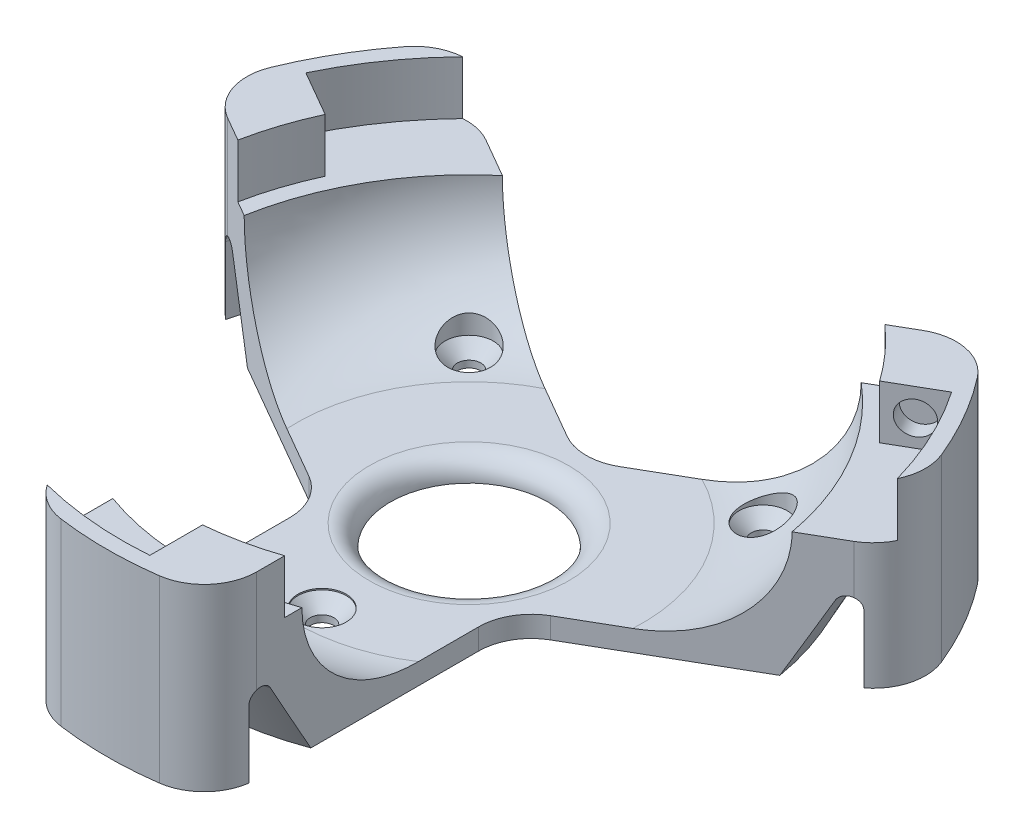
SolidWorks part; units mm, degrees
ref_plane "Front Plane" through (0, 0, 0) normal (0, 0, 1) x (1, 0, 0)
ref_plane "Top Plane" through (0, 0, 0) normal (0, 1, 0) x (1, 0, 0)
ref_plane "Right Plane" through (0, 0, 0) normal (1, 0, 0) x (0, 0, -1)
sketch "Sketch1" plane through (0, 0, 0) normal (0, 1, 0) x (1, 0, 0)
  line L0 (-56, 0) -> (-56, 28)
  line L1 (-28, 0) -> (-28, 28)
  line L3 (-28, 0) -> (-28, 28)
  line L4 (28, 0) -> (28, 28)
  line L5 (28, 0) -> (28, 28)
  line L7 (56, 0) -> (56, 28)
  line L8 (0, 0) -> (0, 28)
  line L9 (56, 0) -> (56, 28)
  line L10 (-56, 28) -> (-56, 56)
  line L11 (-56, 56) -> (-28, 56)
  line L12 (-28, 28) -> (-28, 56)
  line L13 (-28, 28) -> (-28, 56)
  line L15 (0, 56) -> (28, 56)
  line L16 (28, 28) -> (28, 56)
  line L17 (28, 28) -> (28, 56)
  line L18 (28, 56) -> (56, 56)
  line L19 (56, 28) -> (56, 56)
  line L20 (-28, 56) -> (0, 56)
  line L21 (56, 28) -> (56, 56)
  line L23 (0, 28) -> (0, 56)
  line L24 (-56, -28) -> (-56, 0)
  line L25 (-28, -28) -> (-28, 0)
  line L27 (-28, -28) -> (-28, 0)
  line L28 (28, -28) -> (28, 0)
  line L29 (28, -28) -> (28, 0)
  line L31 (56, -28) -> (56, 0)
  line L32 (0, -28) -> (0, 0)
  line L33 (56, -28) -> (56, 0)
  line L34 (-56, 0) -> (-56, 28)
  line L35 (-56, 28) -> (-28, 28)
  line L36 (-28, 0) -> (-28, 28)
  line L37 (-28, 0) -> (-28, 28)
  line L38 (0, 0) -> (0, 28)
  line L39 (0, 28) -> (28, 28)
  line L40 (28, 0) -> (28, 28)
  line L41 (28, 0) -> (28, 28)
  line L42 (28, 28) -> (56, 28)
  line L43 (56, 0) -> (56, 28)
  line L44 (-28, 28) -> (0, 28)
  line L45 (56, 0) -> (56, 28)
  line L46 (0, 0) -> (0, 28)
  line L47 (0, 0) -> (0, 28)
  line L48 (28, -56) -> (56, -56)
  line L49 (0, -56) -> (28, -56)
  line L51 (0, -28) -> (28, -28)
  line L52 (28, -56) -> (28, -28)
  line L53 (28, -56) -> (28, -28)
  line L54 (-28, -56) -> (0, -56)
  line L55 (56, -56) -> (56, -28)
  line L56 (-56, -56) -> (-28, -56)
  line L57 (56, -56) -> (56, -28)
  line L58 (-56, -56) -> (-56, -28)
  line L59 (-56, -28) -> (-28, -28)
  line L60 (28, -28) -> (56, -28)
  line L61 (0, -28) -> (28, -28)
  line L62 (0, -28) -> (0, 0)
  line L63 (0, 0) -> (28, 0)
  line L64 (28, -28) -> (28, 0)
  line L65 (28, -28) -> (28, 0)
  line L66 (28, 0) -> (56, 0)
  line L67 (56, -28) -> (56, 0)
  line L68 (-28, -56) -> (-28, -28)
  line L69 (56, -28) -> (56, 0)
  line L70 (-28, -56) -> (-28, -28)
  line L72 (84, 0) -> (84, 28)
  line L81 (0, -56) -> (0, -28)
  line L82 (-28, -28) -> (0, -28)
  line L83 (-56, -28) -> (-28, -28)
  line L84 (-56, -28) -> (-56, 0)
  line L85 (-56, 0) -> (-28, 0)
  line L86 (-28, -28) -> (-28, 0)
  line L87 (-28, -28) -> (-28, 0)
  line L88 (-28, 0) -> (0, 0)
  line L89 (0, -28) -> (0, 0)
  line L90 (0, -28) -> (0, 0)
  line L92 (0, -56) -> (0, -28)
  line L93 (0, -28) -> (0, 0)
  line L94 (0, 0) -> (0, 28)
  line L95 (0, 28) -> (0, 56)
  dimension "D3" = 3
  dimension "D4" = 2
  dimension "D5" = 3
  dimension "D6" = 2
sketch "Sketch2" plane through (0, 0, 0) normal (0, 1, 0) x (1, 0, 0)
  circle A0 centre (0, 0) radius 53
  circle A1 centre (0, 0) radius 69
  dimension "D1" = 106
  dimension "D2" = 16
extrude "Boss-Extrude1" add sketch "Sketch2" along normal blind 20
sketch "Sketch4" plane through (0, 0, 0) normal (0, 0, 1) x (1, 0, 0)
  line L2 (69, 20) -> (-69, 20) construction
  line L3 (-69, 0) -> (69, 0) construction
  line L4 (53, 20) -> (53, 0)
  line L5 (53, 0) -> (33, 0)
  ellipse E0 centre (33, 20) end of major axis (53, 20) minor radius 20 (33, 0) -> (53, 20) ccw
  dimension "D1" = 20
revolve "Revolve5" add sketch "Sketch4" angle 360 about axis through (0, 20, 0) along (0, -1, 0)
sketch "Sketch5" plane through (0, 0, 0) normal (0, -1, 0) x (1, 0, 0)
  circle A0 centre (0, 0) radius 69
  circle A1 centre (0, 0) radius 69 construction
extrude "Boss-Extrude2" add sketch "Sketch5" along normal blind 4
sketch "Sketch6" plane through (0, -4, 0) normal (0, -1, 0) x (1, 0, 0)
  line L0 (18, 10.3923) -> (18, 58.2838)
  line L1 (-59.4752, -13.5534) -> (-86.3802, -29.087)
  line L2 (-18, 10.3923) -> (-18, 58.2838)
  line L3 (0, -20.7846) -> (41.4752, -44.7304)
  line L4 (18, 10.3923) -> (59.4752, -13.5534)
  line L5 (-41.4752, -44.7304) -> (-68.3802, -60.2639)
  line L6 (0, -20.7846) -> (-41.4752, -44.7304)
  line L7 (-18, 10.3923) -> (-59.4752, -13.5534)
  line L8 (-18, 58.2838) -> (-18, 89.351)
  line L9 (18, 58.2838) -> (18, 89.351)
  line L10 (59.4752, -13.5534) -> (86.3802, -29.087)
  line L11 (41.4752, -44.7304) -> (68.3802, -60.2639)
  arc A0 (-68.3802, -60.2639) -> (68.3802, -60.2639) centre (0, 0) ccw
  arc A1 (86.3802, -29.087) -> (18, 89.351) centre (0, 0) ccw
  arc A2 (-18, 89.351) -> (-86.3802, -29.087) centre (0, 0) ccw
  dimension "D1" = 3
extrude "Cut-Extrude1" cut sketch "Sketch6" against normal through all
sketch "Sketch9" plane through (0, 0, 0) normal (0, 1, 0) x (1, 0, 0)
  circle A0 centre (0, -28) radius 4.6
  circle A1 centre (-28, 28) radius 4.6
  circle A2 centre (28, 28) radius 4.6
  dimension "D1" = 9.2
  dimension "D2" = 9.2
  dimension "D3" = 9.2
extrude "Cut-Extrude2" cut sketch "Sketch9" along normal blind 10 and the other way blind 0.25
sketch "Sketch15" plane through (0, 0, 0) normal (0, 1, 0) x (1, 0, 0)
  circle A0 centre (0, 0) radius 15
  dimension "D1" = 30
extrude "Cut-Extrude5" cut sketch "Sketch15" against normal blind 12
fillet "Fillet1" radius 10 3 edges at (0, -2, -20.7846) (-18, -2, 10.3923) (18, -2, 10.3923)
fillet "Fillet2" radius 10 6 edges at (-48.6867, 8, -48.8939) (-66.6867, 8, -17.7169) (18, 8, 66.6108) (-18, 8, 66.6108) (66.6867, 8, -17.7169) (48.6867, 8, -48.8939)
fillet "Fillet4" radius 4 1 edges at (0, 0, 15)
hole_wizard "CSK for M4 Flat Head Machine Screw3" positions "3DSketch3" profile "Sketch14" countersink size "M4" standard "ANSI Metric" end condition through all
sketch3d "3DSketch3"
  line L0 (0, -0.25, 28) -> (0, 0, 28) construction
  line L1 (-28, -0.25, -28) -> (-28, 2.6999, -28) construction
  line L2 (28, -0.25, -28) -> (28, 2.6947, -28) construction
  point P0 (0, -0.25, 28)
  point P4 (-28, -0.25, -28)
  point P8 (28, -0.25, -28)
sketch "Sketch14" plane through (0, -0.25, 28) normal (1, 0, 0) x (0, 0, 1)
  line L0 (0, 0) -> (0, 3.75)
  line L1 (0, 3.75) -> (2.25, 3.75)
  line L2 (2.25, 3.75) -> (2.25, 2.45)
  line L3 (2.25, 2.45) -> (4.7, 0)
  line L5 (4.7, 0) -> (0, 0)
  line L6 (-2.25, 2.45) -> (-4.7, 0) construction
  line L11 (0, -6.35) -> (0, 107.95) construction
  dimension "Thru Hole Dia." = 4.5
  dimension "Thru Hole Depth" = 3.75
  dimension "Near C'Sink Dia." = 9.4
  dimension "Near C'Sink Angle" = 90
sketch "Sketch16" plane through (0, 20, 0) normal (0, 1, 0) x (1, 0, 0)
  line L0 (-59.7558, 34.5) -> (0, 0) construction
  line L1 (-59.6236, 28.5347) -> (-50.9328, 23.5171)
  line L4 (-34.1712, 40.5133) -> (-41.6236, 44.816)
  line L5 (-59.6236, 13.6391) -> (-52.1712, 9.3364)
  line L7 (-59.6236, 13.6391) -> (-55.0153, 10.9785)
  arc A0 (-54.5259, 42.2839) -> (-63.8819, 26.0789) centre (0, 0) ccw construction
  arc A1 (-50.9328, 23.5171) -> (-55.0153, 10.9785) centre (0, 0) ccw
  arc A2 (-47.3417, 46.1299) -> (-59.6236, 28.5347) centre (0, 0) ccw
  arc A3 (-34.1712, 40.5133) -> (-52.1712, 9.3364) centre (0, 0) ccw construction
  arc A8 (-41.6236, 44.816) -> (-54.5259, 42.2839) centre (-46.6236, 36.1558) ccw
  arc A9 (-54.5259, 42.2839) -> (-63.8819, 26.0789) centre (0, 0) ccw
  arc A10 (-63.8819, 26.0789) -> (-59.6236, 13.6391) centre (-54.6236, 22.2994) ccw
  arc A11 (-34.1712, 40.5133) -> (-52.1712, 9.3364) centre (0, 0) ccw
  arc A12 (-47.3417, 46.1299) -> (-54.5259, 42.2839) centre (-46.6236, 36.1558) ccw
  arc A13 (-54.5259, 42.2839) -> (-63.8819, 26.0789) centre (0, 0) ccw
  arc A14 (-63.8819, 26.0789) -> (-59.6236, 13.6391) centre (-54.6236, 22.2994) ccw
  dimension "D1" = 3.1
  dimension "D2" = 13.1
  dimension "D3" = 5.1
  dimension "D4" = 0
extrude "Boss-Extrude3" add sketch "Sketch16" along normal blind 10.2
sketch "Sketch17" plane through (-2.55, 0, 4.4167) normal (0.5, 0, -0.866) x (-0.866, 0, -0.5)
  line L0 (55.8677, 30.2) -> (55.8677, 20) construction
  line L1 (55.8677, 20) -> (65.903, 20) construction
  circle A0 centre (60.8677, 25) radius 3.1
  dimension "D1" = 6.2
  dimension "D2" = 5
  dimension "D3" = 5
extrude "Cut-Extrude6" cut sketch "Sketch17" against normal blind 3.1
pattern_circular "CirPattern1" count 3 over 360 about axis through (0, 0, 0) along (0, 1, 0) of "Cut-Extrude6", "Boss-Extrude3"
ref_plane "Plane1" through (0, 0, 0) normal (0.5, 0, -0.866) x (-0.866, 0, -0.5)
sketch "Sketch18" plane through (0, 0, 0) normal (0.5, 0, -0.866) x (-0.866, 0, -0.5)
  line L2 (62.4551, -4) -> (62.4551, 16.9115)
  line L3 (58.4551, -4) -> (68.3628, -4) construction
  line L4 (62.4551, 16.9115) -> (51.3952, -4)
  line L5 (16.1658, -4) -> (58.4551, -4) construction
  line L6 (51.3952, -4) -> (62.4551, -4)
revolve "Cut-Revolve1" cut sketch "Sketch18" angle 360 about axis through (0, 20, 0) along (0, -1, 0)
fillet "Fillet5" radius 2 3 edges at (-54.0877, 16.9115, -31.2276) (54.0877, 16.9115, -31.2276) (0, 16.9115, 62.4551)
